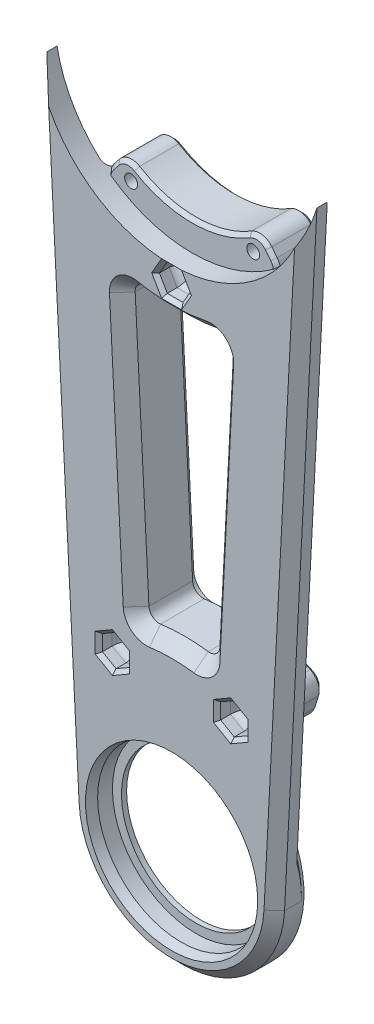
SolidWorks part; units mm, degrees
ref_plane "Front Plane" through (0, 0, 0) normal (0, 0, 1) x (1, 0, 0)
ref_plane "Top Plane" through (0, 0, 0) normal (0, 1, 0) x (1, 0, 0)
ref_plane "Right Plane" through (0, 0, 0) normal (1, 0, 0) x (0, 0, -1)
sketch "Sketch1" plane through (0, 0, 0) normal (0, 0, 1) x (1, 0, 0)
  line L0 (-26.4644, -1.3725) -> (-19.9732, -126.5359)
  line L1 (0, 0) -> (0, -125.5) construction
  line L2 (0, 0) -> (0, 73.3161) construction
  line L3 (0, -125.5) -> (0, -211.5188) construction
  line L5 (26.4644, -1.3725) -> (19.9732, -126.5359)
  arc A0 (26.4644, -1.3725) -> (-26.4644, -1.3725) centre (0, 0) ccw
  arc A1 (-19.9732, -126.5359) -> (19.9732, -126.5359) centre (0, -125.5) ccw
  circle A2 centre (0, -125.5) radius 14.5
  dimension "D2" = 29
  dimension "D4" = 20
  dimension "D6" = 26.5
  dimension "D1" = 125.5
extrude "Boss-Extrude1" add sketch "Sketch1" against normal blind 4
sketch "Sketch3" plane through (0, 0, -4) normal (0, 0, -1) x (-1, 0, 0)
  circle A4 centre (0, -125.5) radius 14.5
  circle A5 centre (0, -125.5) radius 20
  arc A6 (-19.9732, -126.5359) -> (19.9732, -126.5359) centre (0, -125.5) ccw construction
  circle A7 centre (0, -125.5) radius 14.5 construction
extrude "Boss-Extrude3" add sketch "Sketch3" along normal blind 1.75
sketch "Sketch4" plane through (0, 0, 0) normal (0, 0, -1) x (-1, 0, 0)
  circle A1 centre (0, -125.5) radius 16.25
  dimension "D2" = 32.5
chamfer "Chamfer1" distance 1.25 angle 45 1 edges at (0, -105.5, -4)
sketch "Sketch10" plane through (0, 0, 0) normal (0, 0, 1) x (1, 0, 0)
  line L0 (0, 0) -> (0, -183.7144) construction
  circle A0 centre (-19.3911, -144.2879) radius 5.5261
  circle A2 centre (19.3911, -144.2879) radius 5.5261
  circle A3 centre (-19.3911, -144.2879) radius 1.25
  circle A4 centre (19.3911, -144.2879) radius 1.25
  circle A5 centre (0, -125.5) radius 27 construction
  dimension "D1" = 2.5
  dimension "D2" = 54
chamfer "Chamfer2" distance 2 angle 45 4 edges at (-23.2188, -63.9542, 0) (0, -145.5, 0) (0, 26.5, 0) (23.2188, -63.9542, 0)
sketch "Sketch5" plane through (0, 0, -4) normal (0, 0, -1) x (-1, 0, 0)
  circle A0 centre (0, 0) radius 26.75
  dimension "D1" = 53.5
extrude "Cut-Extrude2" cut sketch "Sketch5" against normal blind 10
sketch "Sketch6" plane through (0, 0, 0) normal (0, 0, 1) x (1, 0, 0)
  line L0 (9.7177, -34.6636) -> (6.7874, -91.1644)
  line L1 (-9.7177, -34.6636) -> (-6.7874, -91.1644)
  line L2 (0, 0) -> (0, -127.6021) construction
  line L3 (26.2755, -5.0162) -> (19.9732, -126.5359) construction
  line L4 (-19.9732, -126.5359) -> (-26.2755, -5.0162) construction
  arc A0 (-9.7177, -34.6636) -> (9.7177, -34.6636) centre (0, 0) ccw
  arc A1 (6.7874, -91.1644) -> (-6.7874, -91.1644) centre (0, -125.5) ccw
  dimension "D1" = 35
  dimension "D3" = 36
  dimension "D2" = 15
extrude "Cut-Extrude3" cut sketch "Sketch6" against normal blind 10
fillet "Fillet1" radius 2 4 edges at (-6.7874, -91.1644, -2) (6.7874, -91.1644, -2) (9.7177, -34.6636, -2) (-9.7177, -34.6636, -2)
extrude "Cut-Extrude6" cut sketch "Sketch4" along normal blind 4.75 contours A1
chamfer "Chamfer4" distance 0.5 angle 75 1 edges at (-16.25, -125.5, 0) first distance on face at (-16.25, -125.5, 0)
sketch "Sketch12" plane through (0, 0, -4) normal (0, 0, -1) x (-1, 0, 0)
  line L23 (-6.9033, -88.9303) -> (-9.5789, -37.3396)
  line L25 (9.8993, -89.0857) -> (12.5749, -37.495)
  line L26 (-12.5749, -37.495) -> (-9.8993, -89.0857)
  line L27 (9.8993, -89.0857) -> (12.5749, -37.495)
  line L28 (-12.5749, -37.495) -> (-9.8993, -89.0857)
  line L29 (6.9033, -88.9303) -> (9.5789, -37.3396)
  line L30 (9.5789, -37.3396) -> (6.9033, -88.9303) construction
  line L31 (-6.9033, -88.9303) -> (-9.5789, -37.3396) construction
  arc A0 (4.6408, -90.809) -> (-4.6408, -90.809) centre (0, -125.5) ccw construction
  arc A1 (-7.1826, -35.2762) -> (7.1826, -35.2762) centre (0, 0) ccw construction
  arc A37 (-7.1826, -35.2762) -> (7.1826, -35.2762) centre (0, 0) ccw
  arc A38 (4.6408, -90.809) -> (-4.6408, -90.809) centre (0, -125.5) ccw
  arc A39 (-6.9033, -88.9303) -> (-4.6408, -90.809) centre (-4.906, -88.8267) ccw
  arc A40 (6.9033, -88.9303) -> (4.6408, -90.809) centre (4.906, -88.8267) cw
  arc A41 (9.5789, -37.3396) -> (7.1826, -35.2762) centre (7.5816, -37.236) ccw
  arc A42 (-9.5789, -37.3396) -> (-7.1826, -35.2762) centre (-7.5816, -37.236) cw
  arc A43 (-6.584, -32.3365) -> (-12.5749, -37.495) centre (-7.5816, -37.236) ccw
  arc A44 (-6.584, -32.3365) -> (6.584, -32.3365) centre (0, 0) ccw
  arc A45 (12.5749, -37.495) -> (6.584, -32.3365) centre (7.5816, -37.236) ccw
  arc A46 (4.243, -93.7825) -> (9.8993, -89.0857) centre (4.906, -88.8267) ccw
  arc A47 (-9.8993, -89.0857) -> (-4.243, -93.7825) centre (-4.906, -88.8267) ccw
  arc A48 (4.243, -93.7825) -> (-4.243, -93.7825) centre (0, -125.5) ccw
  arc A49 (-6.584, -32.3365) -> (-12.5749, -37.495) centre (-7.5816, -37.236) ccw
  arc A50 (-6.584, -32.3365) -> (6.584, -32.3365) centre (0, 0) ccw
  arc A51 (12.5749, -37.495) -> (6.584, -32.3365) centre (7.5816, -37.236) ccw
  arc A52 (4.243, -93.7825) -> (9.8993, -89.0857) centre (4.906, -88.8267) ccw
  arc A53 (-9.8993, -89.0857) -> (-4.243, -93.7825) centre (-4.906, -88.8267) ccw
  arc A54 (4.243, -93.7825) -> (-4.243, -93.7825) centre (0, -125.5) ccw
  dimension "D2" = 2
  dimension "D1" = 3
extrude "Boss-Extrude6" add sketch "Sketch12" along normal blind 9
sketch "Sketch14" plane through (0, 0, -4) normal (0, 0, -1) x (-1, 0, 0)
  line L0 (-17.055, -94.9365) -> (-14.385, -103.2442)
  line L1 (17.055, -94.9365) -> (14.385, -103.2442)
  line L2 (0, -125.5) -> (0, 0) construction
  arc A0 (14.385, -103.2442) -> (-14.385, -103.2442) centre (0, -125.5) ccw
  arc A1 (17.055, -94.9365) -> (-17.055, -94.9365) centre (0, -125.5) ccw
  circle A2 centre (-11.5, -97.7917) radius 1.25
  circle A3 centre (11.5, -97.7917) radius 1.25
  circle A4 centre (0, -125.5) radius 30 construction
  arc A8 (4.6408, -90.809) -> (-4.6408, -90.809) centre (0, -125.5) ccw construction
  dimension "D1" = 2.5
  dimension "D2" = 60
  dimension "D3" = 26.5
  dimension "D4" = 23
  dimension "D5" = 28.77
  dimension "D6" = 34.11
extrude "Boss-Extrude7" add sketch "Sketch14" along normal up to surface (9 mm away) up to face at (0, -63.1652, -13)
sketch "Sketch13" plane through (0, 0, -13) normal (0, 0, -1) x (-1, 0, 0)
  line L16 (-11.3765, -37.4328) -> (-8.7009, -89.0235)
  line L17 (8.7009, -89.0235) -> (11.3765, -37.4328)
  line L18 (-11.3765, -37.4328) -> (-8.7009, -89.0235)
  line L19 (8.7009, -89.0235) -> (11.3765, -37.4328)
  arc A36 (11.3765, -37.4328) -> (6.8235, -33.5124) centre (7.5816, -37.236) ccw
  arc A37 (-6.8235, -33.5124) -> (6.8235, -33.5124) centre (0, 0) ccw
  arc A38 (-6.8235, -33.5124) -> (-11.3765, -37.4328) centre (-7.5816, -37.236) ccw
  arc A39 (-8.7009, -89.0235) -> (-4.4021, -92.5931) centre (-4.906, -88.8267) ccw
  arc A40 (4.4021, -92.5931) -> (-4.4021, -92.5931) centre (0, -125.5) ccw
  arc A41 (4.4021, -92.5931) -> (8.7009, -89.0235) centre (4.906, -88.8267) ccw
  arc A42 (11.3765, -37.4328) -> (6.8235, -33.5124) centre (7.5816, -37.236) ccw
  arc A43 (-6.8235, -33.5124) -> (6.8235, -33.5124) centre (0, 0) ccw
  arc A44 (-6.8235, -33.5124) -> (-11.3765, -37.4328) centre (-7.5816, -37.236) ccw
  arc A45 (-8.7009, -89.0235) -> (-4.4021, -92.5931) centre (-4.906, -88.8267) ccw
  arc A46 (4.4021, -92.5931) -> (-4.4021, -92.5931) centre (0, -125.5) ccw
  arc A47 (4.4021, -92.5931) -> (8.7009, -89.0235) centre (4.906, -88.8267) ccw
  dimension "D1" = 1.8
extrude "Cut-Extrude8" cut sketch "Sketch13" against normal blind 2
sketch "Sketch15" plane through (0, 0, -4) normal (0, 0, -1) x (-1, 0, 0)
  line L1 (0, 0) -> (0, -125.5) construction
  line L2 (-13.05, -16.4529) -> (-17.8152, -22.4606)
  line L3 (5.9, -28.0544) -> (5.4653, -32.5443)
  line L4 (13.05, -16.4529) -> (17.8152, -22.4606)
  line L5 (-5.9, -28.0544) -> (-5.4653, -32.5443)
  line L6 (0, 0) -> (-11.875, -20.5681) construction
  line L7 (0, 0) -> (11.875, -20.5681) construction
  arc A1 (-5.4653, -32.5443) -> (5.4653, -32.5443) centre (0, 0) ccw
  circle A3 centre (-11.875, -20.5681) radius 1.25
  circle A4 centre (0, 0) radius 30 construction
  circle A5 centre (0, -30) radius 1.25
  arc A6 (-6.584, -32.3365) -> (6.584, -32.3365) centre (0, 0) ccw construction
  arc A7 (-17.8152, -22.4606) -> (-5.9, -28.0544) centre (0, 0) ccw
  circle A8 centre (0, 0) radius 23.75 construction
  arc A9 (-13.05, -16.4529) -> (13.05, -16.4529) centre (0, 0) ccw
  circle A10 centre (11.875, -20.5681) radius 1.25
  arc A11 (5.9, -28.0544) -> (17.8152, -22.4606) centre (0, 0) ccw
  dimension "D1" = 60
  dimension "D2" = 2.5
  dimension "D4" = 21
  dimension "D5" = 47.5
  dimension "D6" = 2.5
  dimension "D3" = 11.8
  dimension "D7" = 60
  dimension "D8" = 30
  dimension "D9" = 26.1
extrude "Boss-Extrude8" add sketch "Sketch15" along normal up to surface (9 mm away) up to face at (10.25, -97.7917, -13)
fillet "Fillet5" radius 3 14 edges at (-9.0119, -91.6801, -8.5) (-17.055, -94.9365, -8.5) (-14.385, -103.2442, -8.5) (14.385, -103.2442, -8.5) (17.055, -94.9365, -8.5) (9.0119, -91.6801, -8.5) (-5.4653, -32.5443, -8.5) (5.4653, -32.5443, -8.5) (17.8152, -22.4606, -8.5) (13.05, -16.4529, -8.5) (-13.05, -16.4529, -8.5) (-17.8152, -22.4606, -8.5) (-5.9, -28.0544, -8.5) (5.9, -28.0544, -8.5)
fillet "Fillet6" radius 2 25 edges at (-16.2665, -22.9757, -4) (16.2665, -22.9757, -4) (11.5734, -26.2282, -4) (11.458, -34.0779, -4) (-11.458, -34.0779, -4) (-11.2371, -63.2903, -4) (-9.8887, -89.2418, -4) (-10.3051, -91.3225, -4) (-13.2701, -93.1132, -4) (-16.1649, -95.2433, -4) (-15.8883, -98.5666, -4) (-13.838, -101.6016, -4) (0, -99, -4) (13.838, -101.6016, -4) (15.8883, -98.5666, -4) (16.1649, -95.2433, -4) (13.2701, -93.1132, -4) (10.3051, -91.3225, -4) (9.8887, -89.2418, -4) (-11.5734, -26.2282, -4) (11.2371, -63.2903, -4) (-6.5695, -28.3244, -4) (6.6084, -31.3864, -4) (-6.6084, -31.3864, -4) (6.5695, -28.3244, -4)
chamfer "Chamfer5" distance 0.7 angle 45 30 edges at (6.6084, -31.3864, -13) (-6.6084, -31.3864, -13) (11.458, -34.0779, -13) (-11.458, -34.0779, -13) (11.2371, -63.2903, -13) (-11.2371, -63.2903, -13) (9.8887, -89.2418, -13) (-9.8887, -89.2418, -13) (10.3051, -91.3225, -13) (-10.3051, -91.3225, -13) (13.2701, -93.1132, -13) (-13.2701, -93.1132, -13) (16.1649, -95.2433, -13) (-16.1649, -95.2433, -13) (15.8883, -98.5666, -13) (-15.8883, -98.5666, -13) (13.838, -101.6016, -13) (-13.838, -101.6016, -13) (0, -99, -13) (6.5695, -28.3244, -13) (11.5734, -26.2282, -13) (16.4462, -22.3543, -13) (15.3194, -19.3141, -13) (12.9766, -17.5672, -13) (0, -21, -13) (-12.9766, -17.5672, -13) (-15.3194, -19.3141, -13) (-6.5695, -28.3244, -13) (-16.4462, -22.3543, -13) (-11.5734, -26.2282, -13)
chamfer "Chamfer6" distance 0.7 angle 45 7 edges at (-16.1866, -20.5196, -4) (16.1866, -20.5196, -4) (-15.3194, -19.3141, -4) (15.3194, -19.3141, -4) (-12.9766, -17.5672, -4) (12.9766, -17.5672, -4) (0, -21, -4)
sketch "Sketch16" plane through (0, 0, -13) normal (0, 0, -1) x (-1, 0, 0)
  circle A0 centre (11.5, -97.7917) radius 1.25
  circle A1 centre (-11.5, -97.7917) radius 1.25
  circle A2 centre (0, -30) radius 1.25
  circle A3 centre (11.875, -20.5681) radius 1.25 construction
extrude "Cut-Extrude9" cut sketch "Sketch16" against normal blind 24.7
sketch "Sketch17" plane through (0, 0, 0) normal (0, 0, 1) x (1, 0, 0)
  line L1 (11.5, -100.8517) -> (14.15, -99.3217)
  line L2 (14.15, -99.3217) -> (14.15, -96.2617)
  line L3 (14.15, -96.2617) -> (11.5, -94.7317)
  line L4 (11.5, -94.7317) -> (8.85, -96.2617)
  line L5 (8.85, -96.2617) -> (8.85, -99.3217)
  line L6 (8.85, -99.3217) -> (11.5, -100.8517)
  line L7 (-11.5, -100.8517) -> (-8.85, -99.3217)
  line L8 (-8.85, -99.3217) -> (-8.85, -96.2617)
  line L9 (-8.85, -96.2617) -> (-11.5, -94.7317)
  line L10 (-11.5, -94.7317) -> (-14.15, -96.2617)
  line L11 (-14.15, -96.2617) -> (-14.15, -99.3217)
  line L12 (-14.15, -99.3217) -> (-11.5, -100.8517)
  line L19 (-3.06, -30) -> (-1.53, -32.65)
  line L20 (-1.53, -32.65) -> (1.53, -32.65)
  line L21 (1.53, -32.65) -> (3.06, -30)
  line L22 (3.06, -30) -> (1.53, -27.35)
  line L23 (1.53, -27.35) -> (-1.53, -27.35)
  line L24 (-1.53, -27.35) -> (-3.06, -30)
  circle A0 centre (11.5, -97.7917) radius 2.65 construction
  circle A1 centre (-11.5, -97.7917) radius 2.65 construction
  circle A2 centre (0, -30) radius 2.65 construction
  dimension "D2" = 5.3
  dimension "D3" = 5.3
  dimension "D1" = 5.3
extrude "Cut-Extrude10" cut sketch "Sketch17" against normal blind 4
fillet "Fillet7" radius 1.4 18 edges at (-14.15, -97.7917, -4) (-12.825, -95.4967, -4) (-10.175, -95.4967, -4) (-8.85, -97.7917, -4) (-10.175, -100.0867, -4) (-12.825, -100.0867, -4) (8.85, -97.7917, -4) (10.175, -100.0867, -4) (12.825, -100.0867, -4) (14.15, -97.7917, -4) (12.825, -95.4967, -4) (10.175, -95.4967, -4) (-2.295, -31.325, -4) (0, -32.65, -4) (2.295, -31.325, -4) (2.295, -28.675, -4) (0, -27.35, -4) (-2.295, -28.675, -4)
chamfer "Chamfer7" distance 0.7 angle 45 18 edges at (-14.15, -97.7917, 0) (-12.825, -95.4967, 0) (-10.175, -95.4967, 0) (-8.85, -97.7917, 0) (-10.175, -100.0867, 0) (-12.825, -100.0867, 0) (14.15, -97.7917, 0) (12.825, -95.4967, 0) (10.175, -95.4967, 0) (12.825, -100.0867, 0) (10.175, -100.0867, 0) (8.85, -97.7917, 0) (2.295, -31.325, 0) (2.295, -28.675, 0) (0, -27.35, 0) (-2.295, -28.675, 0) (-2.295, -31.325, 0) (0, -32.65, 0)
chamfer "Chamfer8" distance 2.5 angle 45 8 edges at (8.2411, -63.1349, 0) (8.8866, -35.7204, 0) (6.1837, -90.3654, 0) (0, -36, 0) (0, -90.5, 0) (-8.8866, -35.7204, 0) (-6.1837, -90.3654, 0) (-8.2411, -63.1349, 0)
